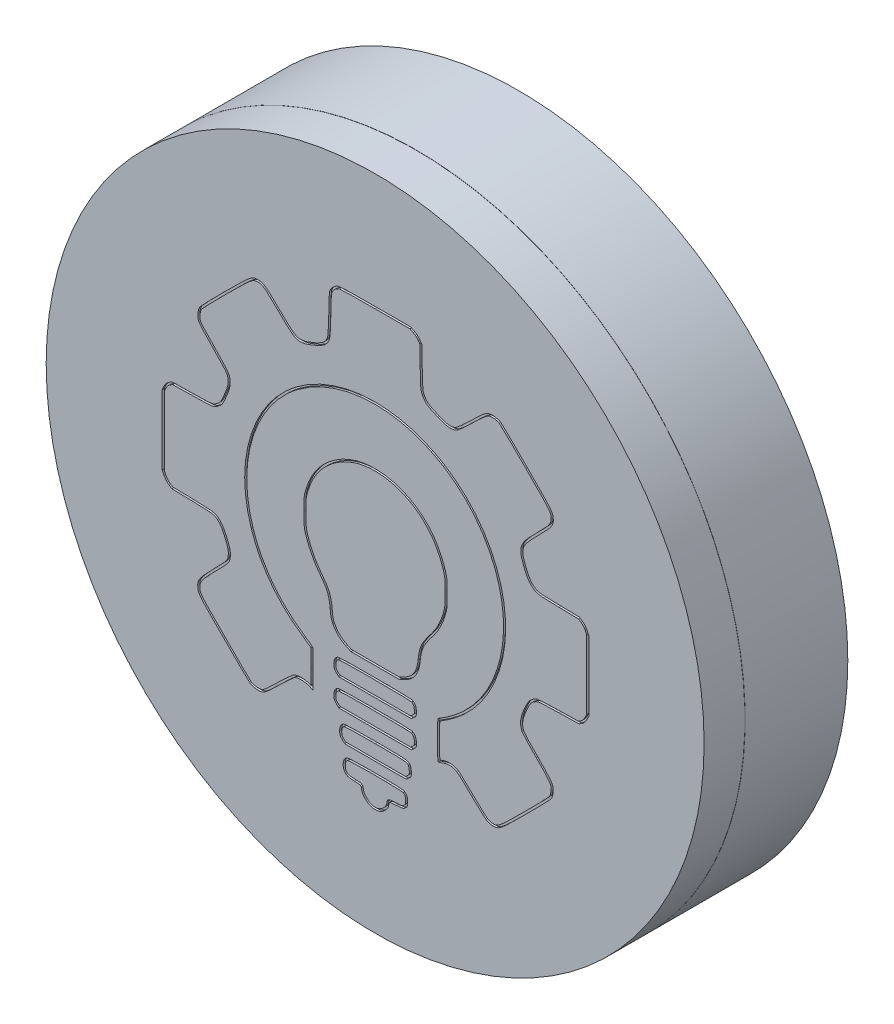
SolidWorks part; units mm, degrees
ref_plane "Front Plane" through (0, 0, 0) normal (0, 0, 1) x (1, 0, 0)
ref_plane "Top Plane" through (0, 0, 0) normal (0, 1, 0) x (1, 0, 0)
ref_plane "Right Plane" through (0, 0, 0) normal (1, 0, 0) x (0, 0, -1)
sketch "Sketch1" plane through (0, 0, 0) normal (0, 0, 1) x (1, 0, 0)
  circle A0 centre (0, 0) radius 15.025
  circle A1 centre (0, 0) radius 16.025
  dimension "D1" = 30.05
  dimension "D2" = 1
extrude "Boss-Extrude1" add sketch "Sketch1" along normal blind 5
sketch "Sketch2" plane through (0, 0, 5) normal (0, 0, 1) x (1, 0, 0)
  circle A0 centre (0, 0) radius 16.025
  circle A1 centre (0, 0) radius 16.025 construction
  point P8 (0, 0)
  circle M3 centre (0, 0) radius 16.025
  circle M4 centre (0, 0) radius 15.025
extrude "Boss-Extrude3" add sketch "Sketch2" along normal blind 2 contours M3 M4 | M4 region at (-15.5717, 0, 5) region at (0, 0, 5)
sketch "Sketch4" plane through (0, 0, 7) normal (0, 0, 1) x (1, 0, 0)
  line L0 (-8.9288, 2.3101) -> (-9.9025, 2.2925)
  line L1 (-9.9025, 2.2925) -> (-10.0506, 2.1937)
  line L2 (-10.287, 1.9115) -> (-10.3717, 1.7281)
  line L3 (-10.3717, 1.7281) -> (-10.3717, 0.0312)
  line L4 (-10.3717, 0.0312) -> (-10.3717, -1.6621)
  line L5 (-10.3717, -1.6621) -> (-10.2835, -1.8421)
  line L6 (-10.0471, -2.1208) -> (-9.9025, -2.2231)
  line L7 (-9.9025, -2.2231) -> (-8.9288, -2.2407)
  line L8 (-3.1997, -7.2043) -> (-3.0339, -7.2819)
  line L9 (-3.0339, -7.2819) -> (-3.0339, -6.3999)
  line L10 (8.9641, -2.2442) -> (9.9378, -2.2231)
  line L11 (9.9378, -2.2231) -> (10.0789, -2.1278)
  line L12 (10.3152, -1.8491) -> (10.407, -1.6621)
  line L13 (10.407, -1.6621) -> (10.407, 0.0312)
  line L14 (10.407, 0.0312) -> (10.407, 1.7281)
  line L15 (10.407, 1.7281) -> (10.3223, 1.9115)
  line L16 (10.0859, 2.1937) -> (9.9378, 2.2925)
  line L17 (9.9378, 2.2925) -> (8.9641, 2.3101)
  line L18 (2.2931, 8.9988) -> (2.2754, 9.9548)
  line L19 (2.2754, 9.9548) -> (2.1802, 10.096)
  line L20 (1.9015, 10.3323) -> (1.7145, 10.424)
  line L21 (1.7145, 10.424) -> (0.0212, 10.4205)
  line L22 (-1.4182, -4.6149) -> (-1.1818, -4.7278)
  line L23 (-1.1818, -4.7278) -> (0, -4.7278)
  line L24 (0, -4.7278) -> (1.1818, -4.7278)
  line L25 (1.1818, -4.7278) -> (1.4182, -4.6149)
  line L26 (-1.8909, -5.966) -> (-1.7709, -6.086)
  line L27 (-1.7709, -6.086) -> (-0.0035, -6.086)
  line L28 (-0.0035, -6.086) -> (1.7604, -6.086)
  line L29 (1.7604, -6.086) -> (1.8874, -5.9766)
  line L30 (-1.8909, -7.2815) -> (-1.7709, -7.4014)
  line L31 (-1.7709, -7.4014) -> (-0.0035, -7.4014)
  line L32 (-0.0035, -7.4014) -> (1.7604, -7.4014)
  line L33 (1.7604, -7.4014) -> (1.8874, -7.292)
  line L34 (-1.6087, -8.6471) -> (-1.4887, -8.7671)
  line L35 (-1.4887, -8.7671) -> (0.0141, -8.7671)
  line L36 (0.0141, -8.7671) -> (1.5134, -8.7671)
  line L37 (1.5134, -8.7671) -> (1.6404, -8.6577)
  line L76 (-8.927, 2.2102) -> (-9.8714, 2.193)
  line L77 (-9.8714, 2.193) -> (-9.9945, 2.111)
  line L78 (-10.1966, 1.8688) -> (-10.2717, 1.7061)
  line L79 (-10.2717, 1.7061) -> (-10.2717, 0.0312)
  line L80 (-10.2717, 0.0312) -> (-10.2717, -1.6389)
  line L81 (-10.2717, -1.6389) -> (-10.194, -1.7973)
  line L82 (-9.9909, -2.0381) -> (-9.8699, -2.1236)
  line L83 (-9.8699, -2.1236) -> (-8.927, -2.1407)
  line L84 (-3.1583, -7.1133) -> (-3.1339, -7.1247)
  line L85 (-3.1339, -7.1247) -> (-3.1339, -6.3999)
  line L86 (8.9619, -2.1442) -> (9.9062, -2.1237)
  line L87 (9.9062, -2.1237) -> (10.0235, -2.0445)
  line L88 (10.2258, -1.8044) -> (10.307, -1.6389)
  line L89 (10.307, -1.6389) -> (10.307, 0.0312)
  line L90 (10.307, 0.0312) -> (10.307, 1.7061)
  line L91 (10.307, 1.7061) -> (10.2319, 1.8688)
  line L92 (10.0298, 2.111) -> (9.9067, 2.193)
  line L93 (9.9067, 2.193) -> (8.9622, 2.2102)
  line L94 (2.1931, 8.997) -> (2.176, 9.9234)
  line L95 (2.176, 9.9234) -> (2.0969, 10.0406)
  line L96 (1.8568, 10.2429) -> (1.6914, 10.324)
  line L97 (1.6914, 10.324) -> (0.0212, 10.3205)
  line L98 (-1.3752, -4.5246) -> (-1.1592, -4.6278)
  line L99 (-1.1592, -4.6278) -> (0, -4.6278)
  line L100 (0, -4.6278) -> (1.1592, -4.6278)
  line L101 (1.1592, -4.6278) -> (1.3753, -4.5245)
  line L102 (-1.8202, -5.8953) -> (-1.7295, -5.986)
  line L103 (-1.7295, -5.986) -> (-0.0035, -5.986)
  line L104 (-0.0035, -5.986) -> (1.7232, -5.986)
  line L105 (1.7232, -5.986) -> (1.8212, -5.9016)
  line L106 (-1.8202, -7.2108) -> (-1.7295, -7.3014)
  line L107 (-1.7295, -7.3014) -> (-0.0035, -7.3014)
  line L108 (-0.0035, -7.3014) -> (1.7232, -7.3014)
  line L109 (1.7232, -7.3014) -> (1.8212, -7.2171)
  line L110 (-1.538, -8.5764) -> (-1.4473, -8.6671)
  line L111 (-1.4473, -8.6671) -> (0.0141, -8.6671)
  line L112 (0.0141, -8.6671) -> (1.4763, -8.6671)
  line L113 (1.4763, -8.6671) -> (1.5743, -8.5827)
  spline S0 degree 3 poles (-1.7815, 10.3817) (-1.9438, 10.3217) (-2.0673, 10.223) (-2.159, 10.0783) knots 0 0 0 0 1 1 1 1
  spline S1 degree 3 poles (-2.159, 10.0783) (-2.2366, 9.9513) (-2.2401, 9.9125) (-2.2578, 8.9953) knots 0 0 0 0 1 1 1 1
  spline S2 degree 3 poles (-2.2578, 8.9953) (-2.2789, 7.944) (-2.2895, 7.8911) (-2.5118, 7.6688) knots 0 0 0 0 1 1 1 1
  spline S3 degree 3 poles (-2.5118, 7.6688) (-2.6564, 7.5207) (-3.2879, 7.249) (-3.5384, 7.2208) knots 0 0 0 0 1 1 1 1
  spline S4 degree 3 poles (-3.5384, 7.2208) (-3.8488, 7.1891) (-3.9582, 7.2631) (-4.6426, 7.944) knots 0 0 0 0 1 1 1 1
  spline S5 degree 3 poles (-4.6426, 7.944) (-5.2811, 8.579) (-5.4398, 8.6919) (-5.6797, 8.6954) knots 0 0 0 0 1 1 1 1
  spline S6 degree 3 poles (-5.6797, 8.6954) (-6.0043, 8.6954) (-6.0149, 8.6884) (-7.2778, 7.4325) knots 0 0 0 0 1 1 1 1
  spline S7 degree 3 poles (-7.2778, 7.4325) (-7.934, 6.7763) (-8.5019, 6.1942) (-8.5408, 6.1307) knots 0 0 0 0 1 1 1 1
  spline S8 degree 3 poles (-8.5408, 6.1307) (-8.6325, 5.9826) (-8.6642, 5.7074) (-8.6078, 5.5345) knots 0 0 0 0 1 1 1 1
  spline S9 degree 3 poles (-8.6078, 5.5345) (-8.5725, 5.4322) (-8.3926, 5.2241) (-7.8987, 4.7231) knots 0 0 0 0 1 1 1 1
  spline S10 degree 3 poles (-7.8987, 4.7231) (-7.1967, 4.0105) (-7.1614, 3.9576) (-7.1614, 3.626) knots 0 0 0 0 1 1 1 1
  spline S11 degree 3 poles (-7.1614, 3.626) (-7.1614, 3.4355) (-7.4189, 2.7829) (-7.5565, 2.61) knots 0 0 0 0 1 1 1 1
  spline S12 degree 3 poles (-7.5565, 2.61) (-7.6165, 2.543) (-7.7294, 2.4477) (-7.807, 2.4054) knots 0 0 0 0 1 1 1 1
  spline S13 degree 3 poles (-7.807, 2.4054) (-7.9481, 2.3348) (-8.0116, 2.3278) (-8.9288, 2.3101) knots 0 0 0 0 1 1 1 1
  spline S14 degree 3 poles (-10.0506, 2.1937) (-10.153, 2.1232) (-10.227, 2.0385) (-10.287, 1.9115) knots 0 0 0 0 1 1 1 1
  spline S15 degree 3 poles (-10.2835, -1.8421) (-10.227, -1.9549) (-10.1388, -2.0608) (-10.0471, -2.1208) knots 0 0 0 0 1 1 1 1
  spline S16 degree 3 poles (-8.9288, -2.2407) (-7.8281, -2.2619) (-7.7929, -2.2689) (-7.5706, -2.5264) knots 0 0 0 0 1 1 1 1
  spline S17 degree 3 poles (-7.5706, -2.5264) (-7.4295, -2.6923) (-7.2108, -3.172) (-7.1649, -3.4296) knots 0 0 0 0 1 1 1 1
  spline S18 degree 3 poles (-7.1649, -3.4296) (-7.1473, -3.5178) (-7.1508, -3.6518) (-7.1684, -3.7506) knots 0 0 0 0 1 1 1 1
  spline S19 degree 3 poles (-7.1684, -3.7506) (-7.2037, -3.9023) (-7.2566, -3.9693) (-7.8528, -4.569) knots 0 0 0 0 1 1 1 1
  spline S20 degree 3 poles (-7.8528, -4.569) (-8.5196, -5.2428) (-8.6395, -5.4122) (-8.6431, -5.6591) knots 0 0 0 0 1 1 1 1
  spline S21 degree 3 poles (-8.6431, -5.6591) (-8.6431, -5.9801) (-8.6289, -5.9978) (-7.3766, -7.2607) knots 0 0 0 0 1 1 1 1
  spline S22 degree 3 poles (-7.3766, -7.2607) (-6.7239, -7.9169) (-6.1419, -8.4849) (-6.0784, -8.5237) knots 0 0 0 0 1 1 1 1
  spline S23 degree 3 poles (-6.0784, -8.5237) (-5.9302, -8.6154) (-5.655, -8.6471) (-5.4822, -8.5907) knots 0 0 0 0 1 1 1 1
  spline S24 degree 3 poles (-5.4822, -8.5907) (-5.3799, -8.5589) (-5.1788, -8.3826) (-4.6919, -7.9028) knots 0 0 0 0 1 1 1 1
  spline S25 degree 3 poles (-4.6919, -7.9028) (-4.3321, -7.55) (-3.9829, -7.229) (-3.9158, -7.1937) knots 0 0 0 0 1 1 1 1
  spline S26 degree 3 poles (-3.9158, -7.1937) (-3.743, -7.102) (-3.4149, -7.109) (-3.1997, -7.2043) knots 0 0 0 0 1 1 1 1
  spline S27 degree 3 poles (-3.0339, -6.3999) (-3.0339, -5.9166) (-3.0304, -5.5109) (-3.0268, -5.4933) knots 0 0 0 0 1 1 1 1
  spline S28 degree 3 poles (-3.0268, -5.4933) (-3.0268, -5.4792) (-3.2068, -5.3451) (-3.4325, -5.1934) knots 0 0 0 0 1 1 1 1
  spline S29 degree 3 poles (-3.4325, -5.1934) (-4.6567, -4.375) (-5.4892, -3.2884) (-5.9408, -1.9197) knots 0 0 0 0 1 1 1 1
  spline S30 degree 3 poles (-5.9408, -1.9197) (-6.7804, 0.6098) (-5.8984, 3.432) (-3.7712, 5.0336) knots 0 0 0 0 1 1 1 1
  spline S31 degree 3 poles (-3.7712, 5.0336) (-1.6898, 6.5964) (1.1183, 6.7163) (3.3338, 5.3334) knots 0 0 0 0 1 1 1 1
  spline S32 degree 3 poles (3.3338, 5.3334) (5.7503, 3.8271) (6.8404, 0.8108) (5.9443, -1.9056) knots 0 0 0 0 1 1 1 1
  spline S33 degree 3 poles (5.9443, -1.9056) (5.5033, -3.2532) (4.6496, -4.3785) (3.4713, -5.1688) knots 0 0 0 0 1 1 1 1
  spline S34 degree 3 poles (3.4713, -5.1688) (3.2738, -5.2993) (3.0974, -5.4122) (3.0727, -5.4192) knots 0 0 0 0 1 1 1 1
  spline S35 degree 3 poles (3.0727, -5.4192) (3.0092, -5.4404) (3.0127, -7.2713) (3.0762, -7.2607) knots 0 0 0 0 1 1 1 1
  spline S36 degree 3 poles (3.0762, -7.2607) (3.1009, -7.2572) (3.2173, -7.2184) (3.3338, -7.1796) knots 0 0 0 0 1 1 1 1
  spline S37 degree 3 poles (3.3338, -7.1796) (3.5631, -7.0949) (3.7712, -7.1055) (3.9688, -7.2043) knots 0 0 0 0 1 1 1 1
  spline S38 degree 3 poles (3.9688, -7.2043) (4.0252, -7.236) (4.3603, -7.5429) (4.7096, -7.8887) knots 0 0 0 0 1 1 1 1
  spline S39 degree 3 poles (4.7096, -7.8887) (5.3516, -8.5237) (5.4928, -8.626) (5.7185, -8.626) knots 0 0 0 0 1 1 1 1
  spline S40 degree 3 poles (5.7185, -8.626) (6.0325, -8.626) (6.0572, -8.6083) (7.3131, -7.3595) knots 0 0 0 0 1 1 1 1
  spline S41 degree 3 poles (7.3131, -7.3595) (7.9693, -6.7069) (8.5372, -6.1248) (8.576, -6.0613) knots 0 0 0 0 1 1 1 1
  spline S42 degree 3 poles (8.576, -6.0613) (8.6148, -6.0013) (8.6536, -5.8708) (8.6678, -5.772) knots 0 0 0 0 1 1 1 1
  spline S43 degree 3 poles (8.6678, -5.772) (8.7066, -5.4439) (8.636, -5.3381) (7.9269, -4.6255) knots 0 0 0 0 1 1 1 1
  spline S44 degree 3 poles (7.9269, -4.6255) (7.553, -4.2515) (7.2708, -3.9376) (7.239, -3.867) knots 0 0 0 0 1 1 1 1
  spline S45 degree 3 poles (7.239, -3.867) (7.1473, -3.6483) (7.172, -3.4225) (7.3201, -3.0521) knots 0 0 0 0 1 1 1 1
  spline S46 degree 3 poles (7.3201, -3.0521) (7.5177, -2.5653) (7.6235, -2.4277) (7.9022, -2.3042) knots 0 0 0 0 1 1 1 1
  spline S47 degree 3 poles (7.9022, -2.3042) (7.9551, -2.2795) (8.3644, -2.2548) (8.9641, -2.2442) knots 0 0 0 0 1 1 1 1
  spline S48 degree 3 poles (10.0789, -2.1278) (10.1706, -2.0678) (10.2553, -1.9691) (10.3152, -1.8491) knots 0 0 0 0 1 1 1 1
  spline S49 degree 3 poles (10.3223, 1.9115) (10.2623, 2.0385) (10.1882, 2.1232) (10.0859, 2.1937) knots 0 0 0 0 1 1 1 1
  spline S50 degree 3 poles (8.9641, 2.3101) (8.0469, 2.3278) (7.9834, 2.3348) (7.8423, 2.4054) knots 0 0 0 0 1 1 1 1
  spline S51 degree 3 poles (7.8423, 2.4054) (7.6306, 2.5183) (7.5071, 2.6911) (7.3413, 3.1039) knots 0 0 0 0 1 1 1 1
  spline S52 degree 3 poles (7.3413, 3.1039) (7.0697, 3.7883) (7.1155, 3.9153) (7.9551, 4.7443) knots 0 0 0 0 1 1 1 1
  spline S53 degree 3 poles (7.9551, 4.7443) (8.5584, 5.3405) (8.6748, 5.4993) (8.6783, 5.7286) knots 0 0 0 0 1 1 1 1
  spline S54 degree 3 poles (8.6783, 5.7286) (8.6783, 6.0496) (8.6642, 6.0672) (7.4119, 7.3302) knots 0 0 0 0 1 1 1 1
  spline S55 degree 3 poles (7.4119, 7.3302) (6.7592, 7.9863) (6.1771, 8.5543) (6.1136, 8.5931) knots 0 0 0 0 1 1 1 1
  spline S56 degree 3 poles (6.1136, 8.5931) (6.0537, 8.6319) (5.9231, 8.6707) (5.8244, 8.6848) knots 0 0 0 0 1 1 1 1
  spline S57 degree 3 poles (5.8244, 8.6848) (5.4963, 8.7236) (5.3834, 8.6531) (4.6743, 7.9511) knots 0 0 0 0 1 1 1 1
  spline S58 degree 3 poles (4.6743, 7.9511) (4.2863, 7.5701) (3.9864, 7.302) (3.9053, 7.2667) knots 0 0 0 0 1 1 1 1
  spline S59 degree 3 poles (3.9053, 7.2667) (3.6901, 7.1785) (3.5101, 7.1996) (3.0903, 7.3725) knots 0 0 0 0 1 1 1 1
  spline S60 degree 3 poles (3.0903, 7.3725) (2.6282, 7.563) (2.5012, 7.6512) (2.3954, 7.8735) knots 0 0 0 0 1 1 1 1
  spline S61 degree 3 poles (2.3954, 7.8735) (2.3142, 8.0357) (2.3107, 8.0851) (2.2931, 8.9988) knots 0 0 0 0 1 1 1 1
  spline S62 degree 3 poles (2.1802, 10.096) (2.1202, 10.1877) (2.0214, 10.2723) (1.9015, 10.3323) knots 0 0 0 0 1 1 1 1
  spline S63 degree 3 poles (0.0212, 10.4205) (-1.083, 10.4205) (-1.7145, 10.4064) (-1.7815, 10.3817) knots 0 0 0 0 1 1 1 1
  spline S64 degree 3 poles (-0.5115, 3.5413) (-1.4499, 3.4073) (-2.3707, 2.8181) (-2.9139, 2.0068) knots 0 0 0 0 1 1 1 1
  spline S65 degree 3 poles (-2.9139, 2.0068) (-3.1327, 1.6751) (-3.2456, 1.4353) (-3.3761, 1.0084) knots 0 0 0 0 1 1 1 1
  spline S66 degree 3 poles (-3.3761, 1.0084) (-3.4643, 0.7262) (-3.4713, 0.6591) (-3.4713, 0.0524) knots 0 0 0 0 1 1 1 1
  spline S67 degree 3 poles (-3.4713, 0.0524) (-3.4713, -0.5615) (-3.4643, -0.6214) (-3.3761, -0.9142) knots 0 0 0 0 1 1 1 1
  spline S68 degree 3 poles (-3.3761, -0.9142) (-3.2526, -1.3129) (-2.981, -1.8421) (-2.7587, -2.1172) knots 0 0 0 0 1 1 1 1
  spline S69 degree 3 poles (-2.7587, -2.1172) (-2.3424, -2.6393) (-2.2366, -2.8792) (-2.1908, -3.4296) knots 0 0 0 0 1 1 1 1
  spline S70 degree 3 poles (-2.1908, -3.4296) (-2.1696, -3.7083) (-2.1414, -3.8317) (-2.0673, -3.9834) knots 0 0 0 0 1 1 1 1
  spline S71 degree 3 poles (-2.0673, -3.9834) (-1.9332, -4.2551) (-1.7004, -4.4808) (-1.4182, -4.6149) knots 0 0 0 0 1 1 1 1
  spline S72 degree 3 poles (1.4182, -4.6149) (1.8979, -4.3891) (2.1414, -4.0187) (2.1943, -3.4331) knots 0 0 0 0 1 1 1 1
  spline S73 degree 3 poles (2.1943, -3.4331) (2.2437, -2.8969) (2.3495, -2.6676) (2.8399, -2.0467) knots 0 0 0 0 1 1 1 1
  spline S74 degree 3 poles (2.8399, -2.0467) (3.0727, -1.7503) (3.2773, -1.3482) (3.4078, -0.9178) knots 0 0 0 0 1 1 1 1
  spline S75 degree 3 poles (3.4078, -0.9178) (3.4996, -0.6179) (3.5066, -0.5615) (3.5066, 0.0524) knots 0 0 0 0 1 1 1 1
  spline S76 degree 3 poles (3.5066, 0.0524) (3.5066, 0.6627) (3.4996, 0.7262) (3.4114, 1.0154) knots 0 0 0 0 1 1 1 1
  spline S77 degree 3 poles (3.4114, 1.0154) (3.2949, 1.3929) (3.0621, 1.8656) (2.8469, 2.1549) knots 0 0 0 0 1 1 1 1
  spline S78 degree 3 poles (2.8469, 2.1549) (2.0849, 3.1886) (0.7832, 3.7248) (-0.5115, 3.5413) knots 0 0 0 0 1 1 1 1
  spline S79 degree 3 poles (-1.8168, -5.2816) (-1.9544, -5.3557) (-2.0108, -5.4616) (-2.0108, -5.6556) knots 0 0 0 0 1 1 1 1
  spline S80 degree 3 poles (-2.0108, -5.6556) (-2.0108, -5.8249) (-1.9967, -5.8602) (-1.8909, -5.966) knots 0 0 0 0 1 1 1 1
  spline S81 degree 3 poles (1.8874, -5.9766) (1.9967, -5.8778) (2.0108, -5.8496) (2.0108, -5.6909) knots 0 0 0 0 1 1 1 1
  spline S82 degree 3 poles (2.0108, -5.6909) (2.0108, -5.4827) (1.9438, -5.3381) (1.8168, -5.2816) knots 0 0 0 0 1 1 1 1
  spline S83 degree 3 poles (1.8168, -5.2816) (1.6933, -5.2252) (-1.7145, -5.2217) (-1.8168, -5.2816) knots 0 0 0 0 1 1 1 1
  spline S84 degree 3 poles (-1.8168, -6.5971) (-1.9544, -6.6712) (-2.0108, -6.777) (-2.0108, -6.971) knots 0 0 0 0 1 1 1 1
  spline S85 degree 3 poles (-2.0108, -6.971) (-2.0108, -7.1404) (-1.9967, -7.1756) (-1.8909, -7.2815) knots 0 0 0 0 1 1 1 1
  spline S86 degree 3 poles (1.8874, -7.292) (1.9967, -7.1933) (2.0108, -7.165) (2.0108, -7.0063) knots 0 0 0 0 1 1 1 1
  spline S87 degree 3 poles (2.0108, -7.0063) (2.0108, -6.8052) (1.9332, -6.65) (1.8098, -6.5935) knots 0 0 0 0 1 1 1 1
  spline S88 degree 3 poles (1.8098, -6.5935) (1.6898, -6.5406) (-1.718, -6.5406) (-1.8168, -6.5971) knots 0 0 0 0 1 1 1 1
  spline S89 degree 3 poles (-1.5346, -7.9628) (-1.6722, -8.0368) (-1.7286, -8.1427) (-1.7286, -8.3367) knots 0 0 0 0 1 1 1 1
  spline S90 degree 3 poles (-1.7286, -8.3367) (-1.7286, -8.506) (-1.7145, -8.5413) (-1.6087, -8.6471) knots 0 0 0 0 1 1 1 1
  spline S91 degree 3 poles (1.6404, -8.6577) (1.7498, -8.5589) (1.7639, -8.5272) (1.7639, -8.3755) knots 0 0 0 0 1 1 1 1
  spline S92 degree 3 poles (1.7639, -8.3755) (1.7639, -8.2838) (1.7463, -8.1638) (1.7216, -8.1144) knots 0 0 0 0 1 1 1 1
  spline S93 degree 3 poles (1.7216, -8.1144) (1.6334, -7.9239) (1.6087, -7.9204) (0.0106, -7.9204) knots 0 0 0 0 1 1 1 1
  spline S94 degree 3 poles (0.0106, -7.9204) (-0.9948, -7.9239) (-1.4852, -7.9345) (-1.5346, -7.9628) knots 0 0 0 0 1 1 1 1
  spline S95 degree 3 poles (-1.3688, -9.3068) (-1.4923, -9.3774) (-1.5522, -9.4868) (-1.5558, -9.6561) knots 0 0 0 0 1 1 1 1
  spline S96 degree 3 poles (-1.5558, -9.6561) (-1.5628, -9.8254) (-1.5275, -9.9136) (-1.4111, -10.0194) knots 0 0 0 0 1 1 1 1
  spline S97 degree 3 poles (-1.4111, -10.0194) (-1.3511, -10.0759) (-1.2665, -10.0935) (-1.0125, -10.1076) knots 0 0 0 0 1 1 1 1
  spline S98 degree 3 poles (-1.0125, -10.1076) (-0.7232, -10.1218) (-0.6879, -10.1323) (-0.6773, -10.1958) knots 0 0 0 0 1 1 1 1
  spline S99 degree 3 poles (-0.6773, -10.1958) (-0.6526, -10.3758) (-0.6279, -10.4322) (-0.5186, -10.5521) knots 0 0 0 0 1 1 1 1
  spline S100 degree 3 poles (-0.5186, -10.5521) (-0.2258, -10.8908) (0.2258, -10.8908) (0.5186, -10.5521) knots 0 0 0 0 1 1 1 1
  spline S101 degree 3 poles (0.5186, -10.5521) (0.6279, -10.4322) (0.6526, -10.3758) (0.6773, -10.1958) knots 0 0 0 0 1 1 1 1
  spline S102 degree 3 poles (0.6773, -10.1958) (0.6879, -10.1323) (0.7232, -10.1253) (1.0301, -10.1076) knots 0 0 0 0 1 1 1 1
  spline S103 degree 3 poles (1.0301, -10.1076) (1.3476, -10.09) (1.3794, -10.0829) (1.4781, -9.9877) knots 0 0 0 0 1 1 1 1
  spline S104 degree 3 poles (1.4781, -9.9877) (1.5699, -9.8995) (1.5875, -9.8572) (1.5875, -9.7161) knots 0 0 0 0 1 1 1 1
  spline S105 degree 3 poles (1.5875, -9.7161) (1.5875, -9.5044) (1.5311, -9.3739) (1.4076, -9.3104) knots 0 0 0 0 1 1 1 1
  spline S106 degree 3 poles (1.4076, -9.3104) (1.2735, -9.2433) (-1.2453, -9.2398) (-1.3688, -9.3068) knots 0 0 0 0 1 1 1 1
  spline S171 degree 3 poles (-9.9945, 2.111) (-10.016, 2.0961) (-10.0581, 2.0634) (-10.1096, 2.0103) (-10.155, 1.9489) (-10.1841, 1.8952) (-10.1966, 1.8688) knots 0.002323 0.002323 0.002323 0.002323 0.251742 0.501161 0.750581 1 1 1 1
  spline S172 degree 3 poles (-10.194, -1.7973) (-10.1815, -1.8224) (-10.1533, -1.8709) (-10.1025, -1.939) (-10.0459, -1.9976) (-10.0105, -2.0252) (-9.9909, -2.0381) knots 0 0 0 0 0.25139 0.502779 0.754169 1.005559 1.005559 1.005559 1.005559
  spline S173 degree 3 poles (-8.927, -2.1407) (-8.8622, -2.142) (-8.7269, -2.1446) (-8.5014, -2.1497) (-8.267, -2.1573) (-8.0555, -2.1716) (-7.8404, -2.202) (-7.652, -2.2805) (-7.5463, -2.4016) (-7.4947, -2.4614) knots -0.000034 -0.000034 -0.000034 -0.000034 0.062489 0.125013 0.250059 0.375105 0.500152 0.750245 1.000338 1.000338 1.000338 1.000338
  spline S174 degree 3 poles (-7.4947, -2.4614) (-7.4718, -2.4883) (-7.4326, -2.5422) (-7.3457, -2.6846) (-7.2387, -2.8972) (-7.1262, -3.1786) (-7.0814, -3.3287) (-7.0667, -3.411) knots -0.000527 -0.000527 -0.000527 -0.000527 0.124393 0.249313 0.499154 0.748994 0.998835 0.998835 0.998835 0.998835
  spline S175 degree 3 poles (-7.0667, -3.411) (-7.061, -3.4396) (-7.0544, -3.4962) (-7.0523, -3.5896) (-7.0576, -3.6843) (-7.0653, -3.7416) (-7.0705, -3.7707) knots 0.003226 0.003226 0.003226 0.003226 0.25457 0.505915 0.757259 1.008604 1.008604 1.008604 1.008604
  spline S176 degree 3 poles (-7.0705, -3.7707) (-7.081, -3.8159) (-7.1061, -3.8986) (-7.1896, -4.0189) (-7.3029, -4.1477) (-7.4192, -4.2712) (-7.5487, -4.404) (-7.6727, -4.5295) (-7.7464, -4.6038) (-7.7818, -4.6394) knots -0.005543 -0.005543 -0.005543 -0.005543 0.245831 0.497206 0.622893 0.74858 0.874267 0.937111 0.999954 0.999954 0.999954 0.999954
  spline S177 degree 3 poles (-7.7818, -4.6394) (-7.8213, -4.6794) (-7.903, -4.7623) (-8.0426, -4.9059) (-8.1904, -5.0622) (-8.3243, -5.2136) (-8.4531, -5.3775) (-8.53, -5.518) (-8.5423, -5.6102) (-8.5431, -5.6599) knots 0.000041 0.000041 0.000041 0.000041 0.062471 0.124902 0.249763 0.374624 0.499485 0.749207 0.998929 0.998929 0.998929 0.998929
  spline S178 degree 3 poles (-8.5431, -5.6599) (-8.5431, -5.6934) (-8.5422, -5.7678) (-8.5296, -5.835) (-8.4939, -5.9176) (-8.4111, -6.0367) (-8.2656, -6.2062) (-8.0455, -6.4398) (-7.7864, -6.7046) (-7.5327, -6.9612) (-7.3791, -7.1162) (-7.3056, -7.1903) knots 0.000773 0.000773 0.000773 0.000773 0.125675 0.250576 0.375478 0.50038 0.625281 0.750183 0.875084 0.937535 0.999986 0.999986 0.999986 0.999986
  spline S179 degree 3 poles (-7.3056, -7.1903) (-7.1534, -7.3434) (-6.8333, -7.663) (-6.5033, -7.9879) (-6.288, -8.1965) (-6.1575, -8.3208) (-6.0804, -8.3921) (-6.037, -8.4297) (-6.0305, -8.4351) (-6.0251, -8.4391) knots 0.000027 0.000027 0.000027 0.000027 0.244111 0.488195 0.610236 0.732278 0.85432 0.915341 0.976362 0.976362 0.976362 0.976362
  spline S180 degree 3 poles (-6.0251, -8.4391) (-5.9917, -8.4596) (-5.9247, -8.487) (-5.778, -8.5183) (-5.6271, -8.5206) (-5.5514, -8.5081) (-5.5125, -8.4954) knots 0.002003 0.002003 0.002003 0.002003 0.251839 0.501675 0.751511 1.001347 1.001347 1.001347 1.001347
  spline S181 degree 3 poles (-5.5125, -8.4954) (-5.5036, -8.4927) (-5.492, -8.4876) (-5.4286, -8.4493) (-5.3113, -8.3552) (-5.1265, -8.1855) (-4.9377, -8.0039) (-4.8183, -7.8869) (-4.762, -7.8315) knots -0.002287 -0.002287 -0.002287 -0.002287 0.123007 0.248301 0.498888 0.749476 0.87477 1.000063 1.000063 1.000063 1.000063
  spline S182 degree 3 poles (-4.762, -7.8315) (-4.6745, -7.7456) (-4.4913, -7.5687) (-4.2531, -7.3461) (-4.0982, -7.2079) (-4.0116, -7.1375) (-3.9812, -7.1151) (-3.9626, -7.1053) knots -0.000086 -0.000086 -0.000086 -0.000086 0.249847 0.499779 0.749712 0.874679 0.999645 0.999645 0.999645 0.999645
  spline S183 degree 3 poles (-3.9626, -7.1053) (-3.9056, -7.0751) (-3.7837, -7.0383) (-3.5723, -7.0224) (-3.3545, -7.0457) (-3.2219, -7.0851) (-3.1583, -7.1133) knots 0.000189 0.000189 0.000189 0.000189 0.250515 0.500841 0.751167 1.001494 1.001494 1.001494 1.001494
  spline S184 degree 3 poles (-3.1339, -6.3999) (-3.1339, -6.3042) (-3.1336, -6.1049) (-3.1324, -5.8534) (-3.131, -5.6865) (-3.1297, -5.5845) (-3.1291, -5.5521) (-3.1286, -5.5336) knots 0 0 0 0 0.206567 0.413133 0.6197 0.722983 0.826266 0.826266 0.826266 0.826266
  spline S185 degree 3 poles (-3.1286, -5.5336) (-3.1478, -5.518) (-3.181, -5.4925) (-3.268, -5.4286) (-3.3692, -5.3574) (-3.4494, -5.3026) (-3.4882, -5.2765) knots 0.27751 0.27751 0.27751 0.27751 0.458097 0.638685 0.819273 0.99986 0.99986 0.99986 0.99986
  spline S186 degree 3 poles (-3.4882, -5.2765) (-3.7904, -5.0745) (-4.3735, -4.6177) (-5.0796, -3.841) (-5.6427, -2.9607) (-5.9237, -2.2908) (-6.0357, -1.9511) knots 0.000025 0.000025 0.000025 0.000025 0.250014 0.500002 0.749991 0.999979 0.999979 0.999979 0.999979
  spline S187 degree 3 poles (-6.0357, -1.9511) (-6.1411, -1.6336) (-6.3016, -0.9762) (-6.4067, 0.338) (-6.1586, 1.9643) (-5.4375, 3.4427) (-4.6038, 4.4633) (-4.0984, 4.9124) (-3.8313, 5.1135) knots 0.000011 0.000011 0.000011 0.000011 0.125011 0.250011 0.50001 0.750009 0.875009 1.000008 1.000008 1.000008 1.000008
  spline S188 degree 3 poles (-3.8313, 5.1135) (-3.5705, 5.3094) (-3.0139, 5.6642) (-1.8414, 6.1804) (-0.2775, 6.482) (1.3077, 6.3138) (2.5224, 5.8984) (3.1092, 5.5915) (3.3867, 5.4183) knots -0.000008 -0.000008 -0.000008 -0.000008 0.124992 0.249993 0.499994 0.749995 0.874996 0.999996 0.999996 0.999996 0.999996
  spline S189 degree 3 poles (3.3867, 5.4183) (3.6895, 5.2295) (4.2674, 4.7951) (5.2291, 3.7725) (6.081, 2.2403) (6.4045, 0.5152) (6.3184, -0.89) (6.1515, -1.5965) (6.0393, -1.9368) knots 0.000004 0.000004 0.000004 0.000004 0.125001 0.249999 0.499995 0.749991 0.874988 0.999986 0.999986 0.999986 0.999986
  spline S190 degree 3 poles (6.0393, -1.9368) (5.9288, -2.2744) (5.6505, -2.9371) (5.087, -3.8242) (4.3848, -4.6066) (3.8219, -5.054) (3.5267, -5.252) knots 0.000028 0.000028 0.000028 0.000028 0.250041 0.500054 0.750068 1.000081 1.000081 1.000081 1.000081
  spline S191 degree 3 poles (3.5267, -5.252) (3.4884, -5.2773) (3.4089, -5.3296) (3.3051, -5.3968) (3.2142, -5.4541) (3.1768, -5.4769) (3.1548, -5.4895) knots -0.000485 -0.000485 -0.000485 -0.000485 0.199236 0.398958 0.598679 0.7984 0.7984 0.7984 0.7984
  spline S192 degree 3 poles (3.1548, -5.4895) (3.1522, -5.5068) (3.1489, -5.5366) (3.1412, -5.6343) (3.134, -5.79) (3.1285, -6.0198) (3.1263, -6.2717) (3.1274, -6.5285) (3.1318, -6.7724) (3.138, -6.9483) (3.1448, -7.0669) (3.1482, -7.111) (3.1504, -7.1348) knots 0.098872 0.098872 0.098872 0.098872 0.1454 0.191929 0.284986 0.378043 0.4711 0.564157 0.657214 0.750271 0.796799 0.843328 0.843328 0.843328 0.843328
  spline S193 degree 3 poles (3.1504, -7.1348) (3.1619, -7.1311) (3.1841, -7.1239) (3.2217, -7.1115) (3.2606, -7.0986) (3.2874, -7.0896) (3.3006, -7.0852) knots 0.536874 0.536874 0.536874 0.536874 0.651594 0.766314 0.881035 0.995755 0.995755 0.995755 0.995755
  spline S194 degree 3 poles (3.3006, -7.0852) (3.361, -7.063) (3.4885, -7.0281) (3.6701, -7.0169) (3.8475, -7.0442) (3.9616, -7.0889) (4.0157, -7.1159) knots 0.002041 0.002041 0.002041 0.002041 0.25245 0.50286 0.753269 1.003679 1.003679 1.003679 1.003679
  spline S195 degree 3 poles (4.0157, -7.1159) (4.0314, -7.1248) (4.0566, -7.1432) (4.136, -7.2089) (4.2829, -7.3408) (4.5139, -7.5574) (4.6942, -7.7327) (4.7799, -7.8176) knots -0.012546 -0.012546 -0.012546 -0.012546 0.11402 0.240587 0.493719 0.746852 0.999985 0.999985 0.999985 0.999985
  spline S196 degree 3 poles (4.7799, -7.8176) (4.818, -7.8552) (4.897, -7.9331) (5.0331, -8.0657) (5.1802, -8.2053) (5.3208, -8.3308) (5.471, -8.4499) (5.5935, -8.517) (5.675, -8.526) (5.7185, -8.526) knots 0.000008 0.000008 0.000008 0.000008 0.062508 0.125007 0.250006 0.375005 0.500004 0.750002 1 1 1 1
  spline S197 degree 3 poles (5.7185, -8.526) (5.7513, -8.526) (5.824, -8.525) (5.8903, -8.5124) (5.9729, -8.4763) (6.0921, -8.3931) (6.2616, -8.2474) (6.4949, -8.0274) (6.759, -7.7685) (7.0146, -7.5152) (7.1688, -7.3619) (7.2426, -7.2886) knots 0 0 0 0 0.125 0.25 0.375 0.499999 0.624999 0.749999 0.874999 0.937499 0.999999 0.999999 0.999999 0.999999
  spline S198 degree 3 poles (7.2426, -7.2886) (7.3956, -7.1364) (7.7151, -6.8166) (8.0398, -6.4867) (8.2484, -6.2714) (8.3727, -6.1408) (8.4442, -6.0636) (8.4818, -6.0202) (8.4874, -6.0136) (8.4914, -6.008) knots 0.000002 0.000002 0.000002 0.000002 0.243936 0.48787 0.609837 0.731803 0.85377 0.914754 0.975737 0.975737 0.975737 0.975737
  spline S199 degree 3 poles (8.4914, -6.008) (8.4997, -5.9952) (8.5104, -5.9733) (8.5361, -5.9041) (8.5563, -5.8282) (8.5652, -5.7827) (8.5686, -5.759) knots -0.00601 -0.00601 -0.00601 -0.00601 0.244357 0.494724 0.745091 0.995458 0.995458 0.995458 0.995458
  spline S200 degree 3 poles (8.5686, -5.759) (8.5726, -5.7248) (8.5788, -5.6502) (8.5702, -5.546) (8.5289, -5.4406) (8.4125, -5.2827) (8.2816, -5.1331) (8.1305, -4.9743) (7.9847, -4.8256) (7.8979, -4.7381) (7.8561, -4.6961) knots 0.001315 0.001315 0.001315 0.001315 0.126145 0.250976 0.500637 0.625467 0.750298 0.875128 0.937544 0.999959 0.999959 0.999959 0.999959
  spline S201 degree 3 poles (7.8561, -4.6961) (7.7673, -4.6073) (7.5815, -4.4172) (7.3688, -4.1897) (7.2137, -4.0074) (7.1667, -3.9499) (7.1473, -3.9069) knots 0.000078 0.000078 0.000078 0.000078 0.251447 0.502815 0.754184 1.005552 1.005552 1.005552 1.005552
  spline S202 degree 3 poles (7.1473, -3.9069) (7.1216, -3.8455) (7.0843, -3.7174) (7.0824, -3.5092) (7.1265, -3.2877) (7.1929, -3.101) (7.2274, -3.0147) knots -0.001811 -0.001811 -0.001811 -0.001811 0.248694 0.499199 0.749703 1.000208 1.000208 1.000208 1.000208
  spline S203 degree 3 poles (7.2274, -3.0147) (7.2505, -2.9579) (7.3005, -2.8385) (7.3875, -2.6527) (7.4974, -2.4698) (7.654, -2.3168) (7.7917, -2.2438) (7.8611, -2.213) knots -0.000158 -0.000158 -0.000158 -0.000158 0.124775 0.249708 0.499574 0.74944 0.999307 0.999307 0.999307 0.999307
  spline S204 degree 3 poles (7.8611, -2.213) (7.9029, -2.194) (7.9763, -2.1884) (8.2068, -2.1679) (8.4813, -2.1565) (8.7413, -2.1487) (8.8899, -2.1455) (8.9619, -2.1442) knots 0.001885 0.001885 0.001885 0.001885 0.251357 0.500829 0.750301 0.875037 0.999773 0.999773 0.999773 0.999773
  spline S205 degree 3 poles (10.0235, -2.0445) (10.043, -2.0318) (10.0786, -2.0043) (10.1334, -1.9481) (10.1831, -1.8818) (10.2128, -1.8304) (10.2258, -1.8044) knots -0.002232 -0.002232 -0.002232 -0.002232 0.248326 0.498884 0.749442 1 1 1 1
  spline S206 degree 3 poles (10.2319, 1.8688) (10.2194, 1.8952) (10.1903, 1.9489) (10.1449, 2.0103) (10.0934, 2.0634) (10.0513, 2.0961) (10.0298, 2.111) knots 0 0 0 0 0.249419 0.498839 0.748258 0.997677 0.997677 0.997677 0.997677
  spline S207 degree 3 poles (8.9622, 2.2102) (8.9079, 2.2112) (8.7948, 2.2134) (8.6054, 2.2175) (8.4076, 2.2225) (8.2294, 2.2293) (8.0528, 2.2407) (7.9111, 2.2632) (7.8363, 2.2966) (7.7964, 2.3165) knots 0 0 0 0 0.062674 0.125347 0.250695 0.376042 0.50139 0.752085 1.00278 1.00278 1.00278 1.00278
  spline S208 degree 3 poles (7.7964, 2.3165) (7.7381, 2.3476) (7.6283, 2.421) (7.491, 2.5745) (7.3902, 2.7467) (7.3112, 2.9148) (7.2683, 3.0174) (7.2484, 3.0668) knots -0.001828 -0.001828 -0.001828 -0.001828 0.248668 0.499164 0.749659 0.874907 1.000155 1.000155 1.000155 1.000155
  spline S209 degree 3 poles (7.2484, 3.0668) (7.2171, 3.1457) (7.1533, 3.314) (7.0993, 3.5161) (7.0857, 3.7134) (7.1284, 3.9053) (7.2274, 4.0939) (7.3804, 4.2937) (7.5587, 4.4874) (7.7318, 4.6637) (7.835, 4.7663) (7.8849, 4.8155) knots -0.000094 -0.000094 -0.000094 -0.000094 0.124917 0.249928 0.374939 0.49995 0.624961 0.749972 0.874983 0.937488 0.999994 0.999994 0.999994 0.999994
  spline S210 degree 3 poles (7.8849, 4.8155) (7.9529, 4.8827) (8.0981, 5.0275) (8.2543, 5.1896) (8.3777, 5.3263) (8.4951, 5.4732) (8.5659, 5.6005) (8.5776, 5.6842) (8.5783, 5.7294) knots 0.000009 0.000009 0.000009 0.000009 0.12485 0.249692 0.374533 0.499375 0.749057 0.99874 0.99874 0.99874 0.99874
  spline S211 degree 3 poles (8.5783, 5.7294) (8.5783, 5.7629) (8.5775, 5.8372) (8.5649, 5.9045) (8.5292, 5.9871) (8.4464, 6.1062) (8.3008, 6.2757) (8.0808, 6.5093) (7.8217, 6.7741) (7.568, 7.0307) (7.4144, 7.1856) (7.3409, 7.2597) knots 0.000837 0.000837 0.000837 0.000837 0.12573 0.250624 0.375518 0.500411 0.625305 0.750199 0.875092 0.937539 0.999986 0.999986 0.999986 0.999986
  spline S212 degree 3 poles (7.3409, 7.2597) (7.1887, 7.4127) (6.8689, 7.7322) (6.539, 8.0569) (6.3237, 8.2655) (6.1932, 8.3898) (6.116, 8.4612) (6.0725, 8.4989) (6.0659, 8.5045) (6.0604, 8.5085) knots 0.000027 0.000027 0.000027 0.000027 0.243955 0.487882 0.609846 0.73181 0.853773 0.914755 0.975737 0.975737 0.975737 0.975737
  spline S213 degree 3 poles (6.0604, 8.5085) (6.0476, 8.5167) (6.0256, 8.5275) (5.9565, 8.5532) (5.8805, 8.5734) (5.835, 8.5823) (5.8114, 8.5857) knots -0.00601 -0.00601 -0.00601 -0.00601 0.244357 0.494724 0.74509 0.995457 0.995457 0.995457 0.995457
  spline S214 degree 3 poles (5.8114, 8.5857) (5.777, 8.5897) (5.7024, 8.5959) (5.5966, 8.5873) (5.4894, 8.5461) (5.3305, 8.4307) (5.1804, 8.3011) (5.0217, 8.1515) (4.8734, 8.0072) (4.7863, 7.9212) (4.7445, 7.8799) knots 0.001315 0.001315 0.001315 0.001315 0.12616 0.251004 0.500693 0.625537 0.750381 0.875225 0.937648 1.00007 1.00007 1.00007 1.00007
  spline S215 degree 3 poles (4.7445, 7.8799) (4.6537, 7.7907) (4.4585, 7.6026) (4.2322, 7.3937) (4.0506, 7.2418) (3.9887, 7.1939) (3.9442, 7.1745) knots -0.000128 -0.000128 -0.000128 -0.000128 0.250901 0.50193 0.752959 1.003988 1.003988 1.003988 1.003988
  spline S216 degree 3 poles (3.9442, 7.1745) (3.8855, 7.1505) (3.7634, 7.1137) (3.5672, 7.1134) (3.3802, 7.1582) (3.207, 7.218) (3.102, 7.2596) (3.0522, 7.28) knots -0.001517 -0.001517 -0.001517 -0.001517 0.248866 0.499248 0.749631 0.874823 1.000014 1.000014 1.000014 1.000014
  spline S217 degree 3 poles (3.0522, 7.28) (2.9986, 7.3022) (2.8856, 7.3498) (2.7111, 7.4304) (2.5412, 7.5267) (2.3985, 7.6591) (2.3332, 7.7716) (2.3055, 7.8296) knots -0.000013 -0.000013 -0.000013 -0.000013 0.124837 0.249687 0.499387 0.749086 0.998786 0.998786 0.998786 0.998786
  spline S218 degree 3 poles (2.3055, 7.8296) (2.2841, 7.8723) (2.2467, 7.9542) (2.2229, 8.0974) (2.2115, 8.2724) (2.205, 8.4483) (2.2002, 8.6436) (2.1963, 8.8311) (2.1941, 8.9432) (2.1931, 8.997) knots 0.001684 0.001684 0.001684 0.001684 0.251271 0.500857 0.625651 0.750444 0.875238 0.937634 1.000031 1.000031 1.000031 1.000031
  spline S219 degree 3 poles (2.0969, 10.0406) (2.0841, 10.0601) (2.0566, 10.0957) (2.0005, 10.1505) (1.9342, 10.2002) (1.8828, 10.2299) (1.8568, 10.2429) knots -0.002232 -0.002232 -0.002232 -0.002232 0.248326 0.498884 0.749442 1 1 1 1
  spline S220 degree 3 poles (0.0212, 10.3205) (-0.104, 10.3205) (-0.3645, 10.3201) (-0.8051, 10.3177) (-1.2576, 10.312) (-1.5593, 10.3025) (-1.6858, 10.2946) (-1.735, 10.2894) (-1.7435, 10.2882) (-1.7496, 10.2869) knots 0 0 0 0 0.119667 0.239334 0.478668 0.718003 0.83767 0.897503 0.957337 0.957337 0.957337 0.957337
  spline S221 degree 3 poles (-1.7496, 10.2869) (-1.7838, 10.2741) (-1.852, 10.2428) (-1.9367, 10.1853) (-2.0106, 10.1151) (-2.0548, 10.0559) (-2.0741, 10.0254) knots 0.006392 0.006392 0.006392 0.006392 0.254344 0.502297 0.75025 0.998202 0.998202 0.998202 0.998202
  spline S222 degree 3 poles (-2.0741, 10.0254) (-2.0881, 10.0026) (-2.1125, 9.9611) (-2.1288, 9.8709) (-2.1397, 9.7099) (-2.146, 9.5402) (-2.1507, 9.3467) (-2.1546, 9.1596) (-2.1568, 9.0472) (-2.1578, 8.9933) knots 0.002001 0.002001 0.002001 0.002001 0.251505 0.501009 0.625761 0.750513 0.875265 0.93764 1.000016 1.000016 1.000016 1.000016
  spline S223 degree 3 poles (-2.1578, 8.9933) (-2.159, 8.9314) (-2.1617, 8.8022) (-2.1669, 8.5861) (-2.1745, 8.3604) (-2.188, 8.1551) (-2.2159, 7.945) (-2.2835, 7.7598) (-2.3879, 7.6513) (-2.4407, 7.5985) knots -0.000014 -0.000014 -0.000014 -0.000014 0.062451 0.124915 0.249845 0.374775 0.499705 0.749564 0.999424 0.999424 0.999424 0.999424
  spline S224 degree 3 poles (-2.4407, 7.5985) (-2.4678, 7.5708) (-2.5255, 7.5266) (-2.6863, 7.4281) (-2.9434, 7.304) (-3.2157, 7.1985) (-3.4099, 7.1417) (-3.4862, 7.1261) (-3.5277, 7.1214) knots 0.000744 0.000744 0.000744 0.000744 0.125736 0.250728 0.500712 0.750696 0.875688 1.00068 1.00068 1.00068 1.00068
  spline S225 degree 3 poles (-3.5277, 7.1214) (-3.6064, 7.1133) (-3.7665, 7.1082) (-3.9599, 7.1937) (-4.1336, 7.3239) (-4.2866, 7.458) (-4.4431, 7.6069) (-4.5879, 7.7488) (-4.6724, 7.8327) (-4.7131, 7.8731) knots -0.000549 -0.000549 -0.000549 -0.000549 0.249587 0.499724 0.624792 0.74986 0.874929 0.937463 0.999997 0.999997 0.999997 0.999997
  spline S226 degree 3 poles (-4.7131, 7.8731) (-4.7509, 7.9107) (-4.8295, 7.9885) (-4.9654, 8.1214) (-5.1134, 8.2619) (-5.2566, 8.389) (-5.4116, 8.511) (-5.5436, 8.583) (-5.6328, 8.5947) (-5.6805, 8.5954) knots 0.000003 0.000003 0.000003 0.000003 0.062432 0.124861 0.249719 0.374577 0.499435 0.749151 0.998866 0.998866 0.998866 0.998866
  spline S227 degree 3 poles (-5.6805, 8.5954) (-5.7145, 8.5954) (-5.7901, 8.5948) (-5.8575, 8.5827) (-5.939, 8.5481) (-6.0569, 8.4666) (-6.2253, 8.322) (-6.4578, 8.1026) (-6.722, 7.8434) (-6.9782, 7.5893) (-7.1331, 7.4353) (-7.2072, 7.3617) knots 0.000785 0.000785 0.000785 0.000785 0.125683 0.250582 0.37548 0.500379 0.625278 0.750176 0.875075 0.937524 0.999974 0.999974 0.999974 0.999974
  spline S228 degree 3 poles (-7.2072, 7.3617) (-7.3602, 7.2086) (-7.6801, 6.8871) (-8.0049, 6.5562) (-8.2136, 6.3405) (-8.3378, 6.2099) (-8.4092, 6.1327) (-8.4468, 6.0894) (-8.4522, 6.0829) (-8.4561, 6.0774) knots 0.00005 0.00005 0.00005 0.00005 0.24413 0.48821 0.61025 0.73229 0.85433 0.915349 0.976369 0.976369 0.976369 0.976369
  spline S229 degree 3 poles (-8.4561, 6.0774) (-8.4766, 6.0442) (-8.5039, 5.9775) (-8.5353, 5.8314) (-8.5377, 5.681) (-8.5256, 5.6053) (-8.513, 5.5665) knots 0.002002 0.002002 0.002002 0.002002 0.250939 0.499876 0.748814 0.997751 0.997751 0.997751 0.997751
  spline S230 degree 3 poles (-8.513, 5.5665) (-8.5096, 5.5567) (-8.5032, 5.5436) (-8.4613, 5.477) (-8.3635, 5.3559) (-8.1893, 5.1661) (-8.0036, 4.9728) (-7.8842, 4.8508) (-7.8275, 4.7933) knots 0.00501 0.00501 0.00501 0.00501 0.129385 0.25376 0.50251 0.75126 0.875634 1.000009 1.000009 1.000009 1.000009
  spline S231 degree 3 poles (-7.8275, 4.7933) (-7.786, 4.7513) (-7.6998, 4.6636) (-7.5556, 4.5158) (-7.406, 4.3591) (-7.2738, 4.2101) (-7.147, 4.0443) (-7.0648, 3.8626) (-7.0614, 3.704) (-7.0614, 3.626) knots -0.000006 -0.000006 -0.000006 -0.000006 0.062494 0.124994 0.249995 0.374996 0.499997 0.749998 1 1 1 1
  spline S232 degree 3 poles (-7.0614, 3.626) (-7.0614, 3.5886) (-7.0717, 3.5198) (-7.1168, 3.3401) (-7.2113, 3.0714) (-7.3259, 2.8067) (-7.4173, 2.6353) (-7.456, 2.5757) (-7.4801, 2.5455) knots 0 0 0 0 0.125544 0.251088 0.502175 0.753263 0.878807 1.00435 1.00435 1.00435 1.00435
  spline S233 degree 3 poles (-7.4801, 2.5455) (-7.4991, 2.5242) (-7.5373, 2.4855) (-7.6102, 2.4209) (-7.6873, 2.3616) (-7.7349, 2.3308) (-7.7607, 2.3167) knots -0.010686 -0.010686 -0.010686 -0.010686 0.243668 0.498022 0.752377 1.006731 1.006731 1.006731 1.006731
  spline S234 degree 3 poles (-7.7607, 2.3167) (-7.8006, 2.2968) (-7.8754, 2.2633) (-8.0171, 2.2407) (-8.1937, 2.2294) (-8.3719, 2.2225) (-8.5698, 2.2175) (-8.7595, 2.2134) (-8.8727, 2.2112) (-8.927, 2.2102) knots -0.003772 -0.003772 -0.003772 -0.003772 0.247181 0.498134 0.623611 0.749087 0.874564 0.937302 1.00004 1.00004 1.00004 1.00004
  spline S250 degree 3 poles (1.3753, -4.5245) (1.4802, -4.4752) (1.6882, -4.347) (1.8933, -4.1156) (2.0109, -3.8652) (2.0699, -3.629) (2.0886, -3.491) (2.0947, -3.424) knots -0.00018 -0.00018 -0.00018 -0.00018 0.249877 0.499934 0.749992 0.87502 1.000049 1.000049 1.000049 1.000049
  spline S251 degree 3 poles (2.0947, -3.424) (2.1006, -3.3594) (2.1156, -3.226) (2.1576, -2.9963) (2.2466, -2.731) (2.4076, -2.4583) (2.5858, -2.2099) (2.7045, -2.0568) (2.7613, -1.9848) knots -0.000054 -0.000054 -0.000054 -0.000054 0.124947 0.249947 0.499947 0.749947 0.874947 0.999947 0.999947 0.999947 0.999947
  spline S252 degree 3 poles (2.7613, -1.9848) (2.8197, -1.9105) (2.9249, -1.7596) (3.0764, -1.4911) (3.2076, -1.2001) (3.2806, -0.9928) (3.3122, -0.8886) knots 0.000114 0.000114 0.000114 0.000114 0.250108 0.500101 0.750095 1.000088 1.000088 1.000088 1.000088
  spline S253 degree 3 poles (3.3122, -0.8886) (3.3224, -0.8551) (3.344, -0.7835) (3.3728, -0.675) (3.3947, -0.5518) (3.4039, -0.3709) (3.4064, -0.1637) (3.4066, -0.016) (3.4066, 0.0524) knots -0.000127 -0.000127 -0.000127 -0.000127 0.124889 0.249905 0.499937 0.749968 0.874984 1 1 1 1
  spline S254 degree 3 poles (3.4066, 0.0524) (3.4066, 0.1204) (3.4064, 0.2673) (3.4039, 0.4744) (3.395, 0.6561) (3.3739, 0.7789) (3.3463, 0.8848) (3.3256, 0.9538) (3.3158, 0.9861) knots 0 0 0 0 0.124977 0.249955 0.49991 0.749864 0.874842 0.999819 0.999819 0.999819 0.999819
  spline S255 degree 3 poles (3.3158, 0.9861) (3.2856, 1.0838) (3.2176, 1.2698) (3.0799, 1.5768) (2.9216, 1.8678) (2.8233, 2.0191) (2.7666, 2.0954) knots 0.00014 0.00014 0.00014 0.00014 0.250155 0.50017 0.750185 1.0002 1.0002 1.0002 1.0002
  spline S256 degree 3 poles (2.7666, 2.0954) (2.5842, 2.3427) (2.1454, 2.7893) (1.3453, 3.2485) (0.4499, 3.4891) (-0.1882, 3.4861) (-0.4974, 3.4423) knots -0.000056 -0.000056 -0.000056 -0.000056 0.249954 0.499964 0.749975 0.999985 0.999985 0.999985 0.999985
  spline S257 degree 3 poles (-0.4974, 3.4423) (-0.7271, 3.4095) (-1.1754, 3.2901) (-1.8192, 2.9646) (-2.3896, 2.5146) (-2.6982, 2.1491) (-2.8307, 1.9514) knots 0.000021 0.000021 0.000021 0.000021 0.249985 0.49995 0.749914 0.999878 0.999878 0.999878 0.999878
  spline S258 degree 3 poles (-2.8307, 1.9514) (-2.8804, 1.876) (-2.98, 1.7167) (-3.09, 1.5035) (-3.1852, 1.2751) (-3.2514, 1.0743) (-3.2805, 0.9789) knots 0.000297 0.000297 0.000297 0.000297 0.25028 0.500263 0.750246 1.000229 1.000229 1.000229 1.000229
  spline S259 degree 3 poles (-3.2805, 0.9789) (-3.2904, 0.9472) (-3.311, 0.8799) (-3.3386, 0.776) (-3.3597, 0.6542) (-3.3687, 0.4727) (-3.3711, 0.2663) (-3.3713, 0.1201) (-3.3713, 0.0524) knots -0.000345 -0.000345 -0.000345 -0.000345 0.124698 0.249741 0.499827 0.749914 0.874957 1 1 1 1
  spline S260 degree 3 poles (-3.3713, 0.0524) (-3.3713, -0.016) (-3.3711, -0.1637) (-3.3687, -0.3713) (-3.3597, -0.553) (-3.3386, -0.6759) (-3.311, -0.7825) (-3.2903, -0.8523) (-3.2804, -0.885) knots 0 0 0 0 0.124946 0.249892 0.499784 0.749676 0.874622 0.999568 0.999568 0.999568 0.999568
  spline S261 degree 3 poles (-3.2804, -0.885) (-3.248, -0.9897) (-3.174, -1.1866) (-3.0177, -1.5221) (-2.8754, -1.7752) (-2.76, -1.9508) (-2.7091, -2.0195) (-2.6807, -2.0546) knots 0.000322 0.000322 0.000322 0.000322 0.250316 0.50031 0.750304 0.875301 1.000298 1.000298 1.000298 1.000298
  spline S262 degree 3 poles (-2.6807, -2.0546) (-2.6317, -2.1161) (-2.5307, -2.2461) (-2.3752, -2.4662) (-2.2317, -2.7213) (-2.1501, -2.985) (-2.1107, -3.2185) (-2.0966, -3.3554) (-2.0911, -3.4216) knots -0.000158 -0.000158 -0.000158 -0.000158 0.12489 0.249937 0.500032 0.750127 0.875174 1.000221 1.000221 1.000221 1.000221
  spline S263 degree 3 poles (-2.0911, -3.4216) (-2.0866, -3.481) (-2.0744, -3.6112) (-2.0525, -3.7358) (-2.0234, -3.838) (-1.9936, -3.9064) (-1.9775, -3.9393) knots -0.000438 -0.000438 -0.000438 -0.000438 0.249562 0.499562 0.749561 0.999561 0.999561 0.999561 0.999561
  spline S264 degree 3 poles (-1.9775, -3.9393) (-1.9465, -4.0022) (-1.8734, -4.1219) (-1.7328, -4.2831) (-1.5663, -4.4204) (-1.4404, -4.4936) (-1.3752, -4.5246) knots 0.000246 0.000246 0.000246 0.000246 0.250213 0.50018 0.750147 1.000114 1.000114 1.000114 1.000114
  spline S270 degree 3 poles (1.8212, -5.9016) (1.8408, -5.8839) (1.8879, -5.8386) (1.8987, -5.8167) (1.9087, -5.7904) (1.9108, -5.7196) (1.9108, -5.6909) knots 0.002759 0.002759 0.002759 0.002759 0.25207 0.50138 0.75069 1 1 1 1
  spline S271 degree 3 poles (1.9108, -5.6909) (1.9108, -5.6498) (1.9036, -5.5609) (1.8746, -5.4708) (1.8338, -5.409) (1.8005, -5.3847) (1.7816, -5.3755) knots 0 0 0 0 0.244396 0.488793 0.733189 0.977586 0.977586 0.977586 0.977586
  spline S272 degree 3 poles (1.7816, -5.3755) (1.7725, -5.3739) (1.759, -5.3723) (1.6943, -5.3664) (1.5804, -5.3603) (1.3926, -5.3536) (1.0889, -5.3463) (0.6283, -5.34) (0.0107, -5.3372) (-0.6079, -5.3391) (-1.0711, -5.3448) (-1.3779, -5.3518) (-1.5684, -5.3584) (-1.6852, -5.3646) (-1.7524, -5.3706) (-1.7677, -5.3725) (-1.7775, -5.3742) knots 0.027754 0.027754 0.027754 0.027754 0.05705 0.086346 0.144938 0.20353 0.262122 0.379306 0.496489 0.613673 0.730857 0.789449 0.848041 0.906633 0.935929 0.965225 0.965225 0.965225 0.965225
  spline S273 degree 3 poles (-1.7775, -5.3742) (-1.8, -5.3869) (-1.8458, -5.4203) (-1.8798, -5.4698) (-1.9048, -5.5381) (-1.9108, -5.6193) (-1.9108, -5.6556) knots 0.024598 0.024598 0.024598 0.024598 0.268449 0.512299 0.75615 1 1 1 1
  spline S274 degree 3 poles (-1.9108, -5.6556) (-1.9108, -5.6872) (-1.9089, -5.7633) (-1.8977, -5.7999) (-1.8844, -5.8279) (-1.8394, -5.8761) (-1.8202, -5.8953) knots 0 0 0 0 0.25 0.5 0.75 1 1 1 1
  spline S280 degree 3 poles (1.8212, -7.2171) (1.8408, -7.1993) (1.8879, -7.1541) (1.8987, -7.1321) (1.9087, -7.1058) (1.9108, -7.0351) (1.9108, -7.0063) knots 0.002759 0.002759 0.002759 0.002759 0.25207 0.50138 0.75069 1 1 1 1
  spline S281 degree 3 poles (1.9108, -7.0063) (1.9108, -6.9669) (1.9028, -6.8834) (1.8716, -6.7905) (1.8261, -6.7226) (1.794, -6.6976) (1.7748, -6.6877) knots 0 0 0 0 0.24253 0.48506 0.72759 0.97012 0.97012 0.97012 0.97012
  spline S282 degree 3 poles (1.7748, -6.6877) (1.7654, -6.6862) (1.751, -6.6846) (1.6856, -6.6792) (1.5711, -6.6735) (1.3832, -6.6675) (1.0797, -6.661) (0.6201, -6.6556) (0.0045, -6.6535) (-0.6119, -6.656) (-1.0734, -6.6618) (-1.3791, -6.6686) (-1.569, -6.675) (-1.6855, -6.6809) (-1.7527, -6.6866) (-1.7683, -6.6884) (-1.7782, -6.69) knots 0.0294 0.0294 0.0294 0.0294 0.058625 0.087851 0.146302 0.204753 0.263205 0.380107 0.49701 0.613913 0.730815 0.789267 0.847718 0.906169 0.935395 0.96462 0.96462 0.96462 0.96462
  spline S283 degree 3 poles (-1.7782, -6.69) (-1.8006, -6.7028) (-1.8461, -6.736) (-1.8799, -6.7855) (-1.9048, -6.8538) (-1.9108, -6.9348) (-1.9108, -6.971) knots 0.026807 0.026807 0.026807 0.026807 0.270105 0.513403 0.756702 1 1 1 1
  spline S284 degree 3 poles (-1.9108, -6.971) (-1.9108, -7.0026) (-1.9089, -7.0787) (-1.8977, -7.1153) (-1.8844, -7.1433) (-1.8394, -7.1915) (-1.8202, -7.2108) knots 0 0 0 0 0.25 0.5 0.75 1 1 1 1
  spline S291 degree 3 poles (1.5743, -8.5827) (1.5938, -8.5651) (1.6403, -8.52) (1.6519, -8.4967) (1.6618, -8.4704) (1.6639, -8.403) (1.6639, -8.3755) knots 0.002777 0.002777 0.002777 0.002777 0.252082 0.501388 0.750694 1 1 1 1
  spline S292 degree 3 poles (1.6639, -8.3755) (1.6639, -8.3538) (1.6618, -8.3114) (1.654, -8.2424) (1.6403, -8.1801) (1.6361, -8.1671) (1.6314, -8.1578) knots 0 0 0 0 0.252269 0.504538 0.756807 1.009076 1.009076 1.009076 1.009076
  spline S293 degree 3 poles (1.6314, -8.1578) (1.6235, -8.1407) (1.6018, -8.0985) (1.591, -8.0889) (1.5484, -8.0655) (1.4356, -8.0443) (1.2439, -8.0305) (0.959, -8.0232) (0.6264, -8.021) (0.3014, -8.0204) (0.1048, -8.0204) (0.0108, -8.0204) knots -0.002387 -0.002387 -0.002387 -0.002387 0.122907 0.2482 0.373494 0.498788 0.624082 0.749376 0.87467 0.937316 0.999963 0.999963 0.999963 0.999963
  spline S294 degree 3 poles (0.0108, -8.0204) (-0.0978, -8.0208) (-0.3246, -8.0218) (-0.7001, -8.0247) (-1.0801, -8.0303) (-1.3257, -8.0382) (-1.4545, -8.0482) (-1.477, -8.0507) (-1.4931, -8.0541) knots 0.000058 0.000058 0.000058 0.000058 0.114785 0.229512 0.458966 0.688421 0.803148 0.917875 0.917875 0.917875 0.917875
  spline S295 degree 3 poles (-1.4931, -8.0541) (-1.516, -8.0669) (-1.5628, -8.1004) (-1.5972, -8.1501) (-1.6225, -8.2185) (-1.6286, -8.3002) (-1.6286, -8.3367) knots 0.017891 0.017891 0.017891 0.017891 0.263419 0.508946 0.754473 1 1 1 1
  spline S296 degree 3 poles (-1.6286, -8.3367) (-1.6286, -8.3683) (-1.6267, -8.4444) (-1.6154, -8.481) (-1.6022, -8.509) (-1.5572, -8.5572) (-1.538, -8.5764) knots 0 0 0 0 0.25 0.5 0.75 1 1 1 1
  spline S309 degree 3 poles (-1.3263, -9.3978) (-1.3468, -9.4102) (-1.387, -9.4414) (-1.4227, -9.4927) (-1.4479, -9.5586) (-1.4551, -9.6276) (-1.4558, -9.6592) knots 0.024993 0.024993 0.024993 0.024993 0.269257 0.513521 0.757784 1.002048 1.002048 1.002048 1.002048
  spline S310 degree 3 poles (-1.4558, -9.6592) (-1.4572, -9.6918) (-1.4558, -9.7651) (-1.4386, -9.8259) (-1.4108, -9.8784) (-1.3651, -9.9262) (-1.3432, -9.946) knots -0.002047 -0.002047 -0.002047 -0.002047 0.248923 0.499892 0.750862 1.001832 1.001832 1.001832 1.001832
  spline S311 degree 3 poles (-1.3432, -9.946) (-1.3352, -9.9536) (-1.3205, -9.9647) (-1.2724, -9.982) (-1.1891, -9.9945) (-1.0971, -10.0024) (-1.036, -10.0062) (-1.0073, -10.0078) knots -0.003499 -0.003499 -0.003499 -0.003499 0.247264 0.498027 0.74879 0.874172 0.999554 0.999554 0.999554 0.999554
  spline S312 degree 3 poles (-1.0073, -10.0078) (-0.9743, -10.0094) (-0.9035, -10.0131) (-0.8012, -10.0208) (-0.7128, -10.0315) (-0.6258, -10.0697) (-0.585, -10.1432) (-0.5808, -10.1669) (-0.5785, -10.1808) knots 0.000388 0.000388 0.000388 0.000388 0.12627 0.252152 0.503915 0.755679 0.881561 1.007443 1.007443 1.007443 1.007443
  spline S313 degree 3 poles (-0.5785, -10.1808) (-0.5735, -10.2166) (-0.5603, -10.2981) (-0.5394, -10.3574) (-0.5119, -10.4075) (-0.4651, -10.4623) (-0.4438, -10.4857) knots -0.002638 -0.002638 -0.002638 -0.002638 0.248698 0.500035 0.751372 1.002709 1.002709 1.002709 1.002709
  spline S314 degree 3 poles (-0.4438, -10.4857) (-0.3849, -10.5538) (-0.2315, -10.6746) (0, -10.7219) (0.2315, -10.6746) (0.3849, -10.5538) (0.4438, -10.4857) knots -0.000982 -0.000982 -0.000982 -0.000982 0.249509 0.5 0.750491 1.000982 1.000982 1.000982 1.000982
  spline S315 degree 3 poles (0.4438, -10.4857) (0.4651, -10.4623) (0.5119, -10.4075) (0.5394, -10.3574) (0.5603, -10.2981) (0.5735, -10.2166) (0.5785, -10.1808) knots -0.002709 -0.002709 -0.002709 -0.002709 0.248628 0.499965 0.751302 1.002638 1.002638 1.002638 1.002638
  spline S316 degree 3 poles (0.5785, -10.1808) (0.5808, -10.1667) (0.5849, -10.1427) (0.6291, -10.0671) (0.7167, -10.0331) (0.8074, -10.0224) (0.9148, -10.0142) (0.9897, -10.0098) (1.0245, -10.0078) knots -0.007443 -0.007443 -0.007443 -0.007443 0.118501 0.244444 0.49633 0.748217 0.87416 1.000104 1.000104 1.000104 1.000104
  spline S317 degree 3 poles (1.0245, -10.0078) (1.0596, -10.0059) (1.1359, -10.0014) (1.24, -9.9937) (1.3224, -9.9791) (1.3505, -9.9676) (1.3922, -9.9317) (1.4088, -9.9157) knots -0.0001 -0.0001 -0.0001 -0.0001 0.124934 0.249968 0.500037 0.750105 1.000173 1.000173 1.000173 1.000173
  spline S318 degree 3 poles (1.4088, -9.9157) (1.4251, -9.9) (1.4625, -9.8606) (1.4748, -9.8353) (1.4852, -9.8036) (1.4875, -9.7419) (1.4875, -9.7161) knots -0.000187 -0.000187 -0.000187 -0.000187 0.24986 0.499907 0.749953 1 1 1 1
  spline S319 degree 3 poles (1.4875, -9.7161) (1.4875, -9.6743) (1.4813, -9.5825) (1.4552, -9.4962) (1.4196, -9.4386) (1.3856, -9.4122) (1.3669, -9.402) knots 0 0 0 0 0.244931 0.489862 0.734793 0.979724 0.979724 0.979724 0.979724
  spline S320 degree 3 poles (1.3669, -9.402) (1.3599, -9.4003) (1.3493, -9.3985) (1.2985, -9.3919) (1.1747, -9.3818) (0.9049, -9.3698) (0.4887, -9.3609) (0.0252, -9.3574) (-0.4385, -9.3594) (-0.8577, -9.3672) (-1.1255, -9.3774) (-1.2781, -9.3903) (-1.3065, -9.3935) (-1.3263, -9.3978) knots 0.029303 0.029303 0.029303 0.029303 0.058566 0.087829 0.146355 0.263408 0.38046 0.497512 0.614565 0.731617 0.84867 0.907196 0.965722 0.965722 0.965722 0.965722
extrude "Cut-Extrude1" cut sketch "Sketch4" against normal blind 0.1
sketch "Sketch6" plane through (0, 0, 5) normal (0, 0, -1) x (-1, 0, 0)
  circle A0 centre (0, 0) radius 16.015
  circle A1 centre (0, 0) radius 16.025
  circle A2 centre (0, 0) radius 16.025 construction
  dimension "D1" = 0.01
extrude "Cut-Extrude3" cut sketch "Sketch6" against normal blind 0.01
